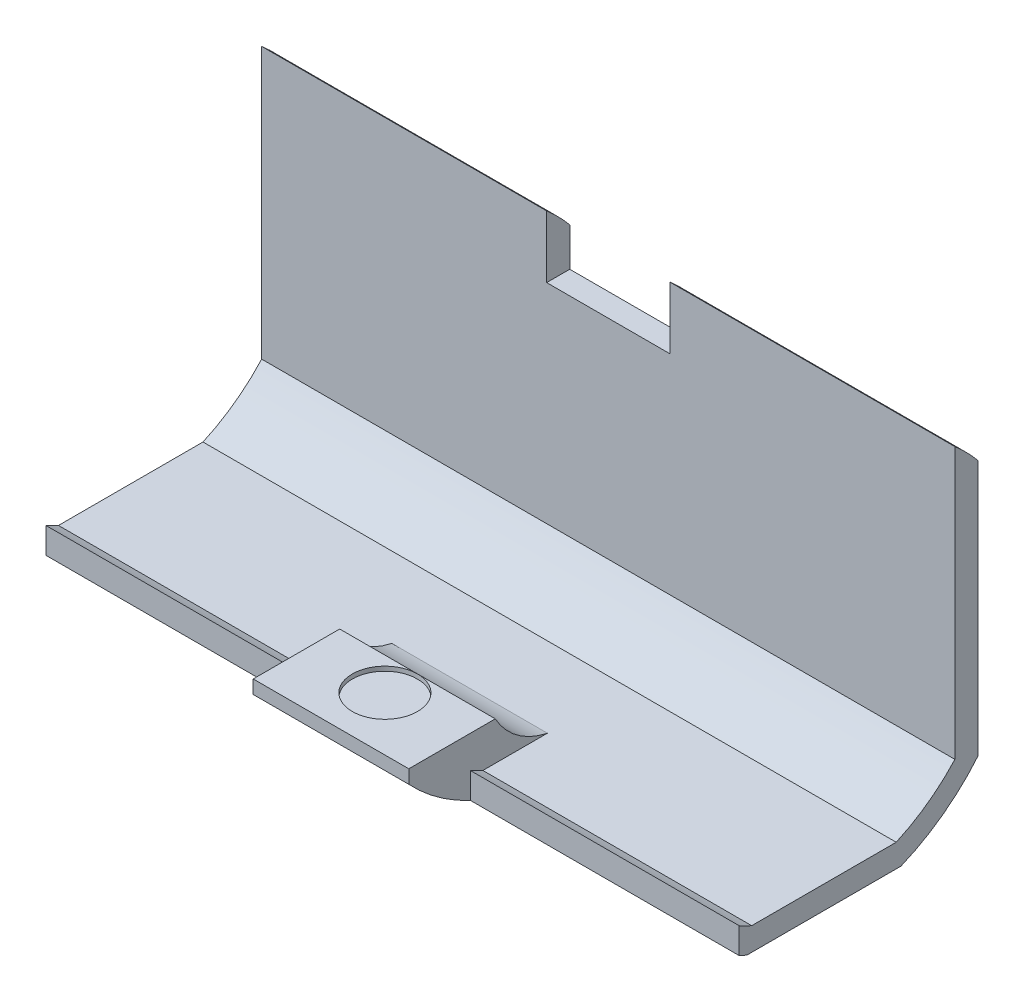
SolidWorks part; units mm, degrees
ref_plane "Plano frontal" through (0, 0, 0) normal (0, 0, 1) x (1, 0, 0)
ref_plane "Plano superior" through (0, 0, 0) normal (0, 1, 0) x (1, 0, 0)
ref_plane "Plano direito" through (0, 0, 0) normal (1, 0, 0) x (0, 0, -1)
sketch "Esboço2" plane through (0, 0, 0) normal (0, 0, 1) x (1, 0, 0)
  line L0 (0, 47.2571) -> (8.5, 47.2571)
  line L1 (0, 47.2571) -> (-8.5, 47.2571)
  line L2 (0, 23.9177) -> (8.5, 23.9177)
  line L3 (0, 23.9177) -> (-8.5, 23.9177)
  line L4 (0, 8.4) -> (0, 75) construction
  line L5 (0, 56.3545) -> (-16, 56.3545) construction
  line L6 (0, 56.3545) -> (16, 56.3545) construction
  line L7 (8.5, 47.2571) -> (8.5, 23.9177)
  line L8 (-8.5, 47.2571) -> (-8.5, 23.9177)
  line L20 (19.3117, 92) -> (-19.3117, 92)
  line L21 (-19.3117, 92) -> (-36.5, 70)
  line L22 (-36.5, 70) -> (-36.5, 0)
  line L23 (-36.5, 0) -> (-22.5, 0)
  line L24 (-22.5, 0) -> (-22.5, 8.4)
  line L25 (-22.5, 8.4) -> (22.5, 8.4)
  line L26 (22.5, 8.4) -> (22.5, 0)
  line L27 (22.5, 0) -> (36.5, 0)
  line L28 (36.5, 0) -> (36.5, 70)
  line L29 (36.5, 70) -> (19.3117, 92)
  circle A8 centre (29.2, 62) radius 2
  circle A9 centre (29.2, 49) radius 2
  circle A10 centre (29.2, 36) radius 2
  circle A11 centre (29.2, 23) radius 2
  circle A12 centre (-29.2, 23) radius 2
  circle A13 centre (0, 75) radius 2
  circle A14 centre (-7, 83.3) radius 2
  circle A15 centre (7, 83.3) radius 2
  circle A16 centre (-29.2, 36) radius 2
  circle A17 centre (-29.2, 49) radius 2
  circle A18 centre (-29.2, 62) radius 2
  circle A20 centre (-29.2, 10) radius 2
  circle A21 centre (29.2, 10) radius 2
  circle A26 centre (-16, 56.3545) radius 2.0867
  circle A27 centre (16, 56.3545) radius 2.0867
  point P31 (0, 23.9177)
  point P33 (0, 47.2571)
sketch "Model" plane through (0, 0, 0) normal (0, 0, 1) x (1, 0, 0)
  line L0 (-13.5, 51.7) -> (0, 51.7) construction
  line L1 (-22.5, 41.7) -> (0, 41.7) construction
  line L2 (0, 50.7729) -> (-23, 50.7729) construction
  line L3 (-22.5, 61.7) -> (-22.5, 41.7) construction
  line L4 (-22.5, 61.7) -> (0, 61.7) construction
  line L5 (-22.5, 61.7) -> (-21, 61.7) construction
  line L6 (-21, 61.7) -> (-21, 43.2) construction
  line L7 (0, 61.7) -> (0, 41.7) construction
  line L8 (0, 61.7) -> (0, 59.2) construction
  line L9 (0, 44.2) -> (0, 59.2)
  line L10 (-23, 63.7) -> (-23, 39.7)
  line L11 (-5.2, 59.2) -> (-0.8, 59.2) construction
  line L12 (-23, 63.7) -> (-5.55, 63.7)
  line L13 (0, 41.7) -> (0, 42.7) construction
  line L14 (-5.55, 63.7) -> (-5.55, 59.2)
  line L15 (0, 42.7) -> (-3.75, 42.7) construction
  line L16 (-3, 57) -> (-3, 61.4) construction
  line L17 (0, 59.2) -> (-5.55, 59.2)
  line L18 (-3, 61.4) -> (0, 61.4) construction
  line L19 (-3, 57) -> (0, 57) construction
  line L20 (-3.75, 41.7) -> (-3.75, 43.7) construction
  line L21 (0, 51.7) -> (-23, 51.7) construction
  line L22 (-3.75, 43.7) -> (0, 43.7) construction
  line L23 (-23, 39.7) -> (-5.55, 39.7)
  line L24 (-3.75, 41.7) -> (-3.75, 34.7) construction
  line L25 (-3.75, 34.7) -> (0, 34.7) construction
  line L26 (-5.55, 39.7) -> (-5.55, 44.2)
  line L27 (0, 44.2) -> (-5.55, 44.2)
  line L34 (-9.5, 39.7) -> (-17.5, 39.7) construction
  line L35 (-17.5, 39.7) -> (-25.5, 47.7) construction
  line L36 (-25.5, 47.7) -> (-25.5, 55.7) construction
  line L37 (-25.5, 55.7) -> (-17.5, 63.7) construction
  line L38 (-17.5, 63.7) -> (-9.5, 63.7) construction
  line L39 (-9.5, 63.7) -> (-5.55, 59.2) construction
  line L40 (-3, 46.75) -> (0, 46.75) construction
  line L41 (-3, 56.65) -> (0, 56.65) construction
  line L42 (-5.55, 44.2) -> (-5.55, 41.2) construction
  line L44 (-2.5, 36.75) -> (-5.55, 41.2) construction
  line L45 (-2.5, 36.75) -> (-2.5, 31.7) construction
  line L48 (-9.5, 31.7) -> (-9.5, 39.7) construction
  line L50 (-2.5, 31.7) -> (-2.5, 29.7) construction
  line L51 (-2.5, 29.7) -> (-9.5, 29.7) construction
  line L52 (-9.5, 29.7) -> (-9.5, 31.7) construction
  line L56 (-36.5, 50.7729) -> (-23.5, 50.7729) construction
  line L57 (-36.5, 70) -> (-36.5, 0) construction
  line L58 (0, 8.4) -> (0, 75) construction
  circle A0 centre (-13.5, 51.7) radius 8.35
  circle A2 centre (-21, 43.2) radius 1 construction
  circle A4 centre (-3, 59.2) radius 2.2 construction
  circle A7 centre (-13.5, 51.7) radius 8 construction
  arc A10 (-5.55, 59.2) -> (-3, 56.65) centre (-3, 59.2) ccw construction
  arc A11 (-3, 46.75) -> (-5.55, 44.2) centre (-3, 44.2) ccw construction
extrude "Ressalto-extrusão2" add sketch "Model" along normal blind 4
sketch "Esboço5" plane through (0, 0, 0) normal (0, 0, -1) x (-1, 0, 0)
  line L1 (23, 63.7) -> (25, 63.7)
  line L2 (23, 63.7) -> (23, 39.7)
  line L3 (23, 39.7) -> (25, 39.7)
  line L4 (25, 63.7) -> (25, 39.7)
extrude "Ressalto-extrusão3" add sketch "Esboço5" against normal blind 20
sketch "Esboço6" plane through (-25, 0, 0) normal (-1, 0, 0) x (0, 0, 1)
  line L0 (0, 51.7) -> (20, 51.7) construction
  line L1 (0, 39.7) -> (0, 63.7) construction
  line L2 (20, 39.7) -> (20, 63.7) construction
  line L3 (20, 51.7) -> (10, 63.7) construction
  line L4 (20, 63.7) -> (0, 63.7) construction
  line L5 (10, 63.7) -> (10, 39.7) construction
  line L6 (20, 39.7) -> (0, 39.7) construction
  circle A0 centre (10, 51.7) radius 13
extrude "Corte-extrusão1" cut sketch "Esboço6" against normal through all flip side to cut
sketch "Esboço8" plane through (-25, 0, 0) normal (-1, 0, 0) x (0, 0, 1)
  line L0 (10, 63.7) -> (10, 39.7) construction
  line L1 (15, 63.7) -> (5, 63.7) construction
  line L2 (15, 39.7) -> (5, 39.7) construction
  line L3 (10, 39.7) -> (0, 51.7) construction
  line L4 (0, 43.3934) -> (0, 60.0066) construction
  line L5 (0, 51.7) -> (20, 51.7) construction
  line L6 (20, 43.3934) -> (20, 60.0066) construction
  line L7 (10, 51.7) -> (7.885, 51.7) construction
  line L8 (10, 51.7) -> (8.5045, 53.1955) construction
  line L9 (10, 51.7) -> (10, 53.815) construction
  line L10 (10, 51.7) -> (11.4955, 53.1955) construction
  line L11 (10, 51.7) -> (12.115, 51.7) construction
  line L12 (10, 51.7) -> (11.4955, 50.2045) construction
  line L13 (10, 51.7) -> (10, 49.585) construction
  line L14 (10, 51.7) -> (8.5045, 50.2045) construction
  line L15 (7.885, 51.7) -> (10, 49.585)
  line L16 (10, 49.585) -> (12.115, 51.7)
  line L17 (12.115, 51.7) -> (10, 53.815)
  line L18 (10, 53.815) -> (7.885, 51.7)
  circle A0 centre (10, 51.7) radius 2.115 construction
  point P24 (10, 51.7)
  dimension "D1" = 8
extrude "Corte-extrusão2" cut sketch "Esboço8" against normal through all
mirror "Espelhar1" about plane through (0, 44.2, 4) normal (-1, 0, 0) of bodies 105
sketch "Esboço9" plane through (0, 0, 4) normal (0, 0, 1) x (1, 0, 0)
  line L0 (0, 59.2) -> (4, 59.2)
  line L1 (5.55, 59.2) -> (-5.55, 59.2) construction
  line L2 (4, 59.2) -> (4, 44.2)
  line L3 (-5.55, 44.2) -> (5.55, 44.2) construction
  line L4 (4, 44.2) -> (-4, 44.2)
  line L5 (-4, 44.2) -> (-4, 59.2)
  line L6 (-4, 59.2) -> (0, 59.2)
extrude "Ressalto-extrusão4" add sketch "Esboço9" along normal blind 4
sketch "Esboço10" plane through (0, 59.2, 0) normal (0, 1, 0) x (1, 0, 0)
  line L0 (0, 0) -> (0, -8) construction
  line L1 (4, -8) -> (-4, -8) construction
  line L2 (0, -4) -> (2.115, -4) construction
  line L3 (0, -4) -> (1.4955, -5.4955) construction
  line L4 (0, -4) -> (0, -6.115) construction
  line L5 (0, -4) -> (-1.4955, -5.4955) construction
  line L6 (0, -4) -> (-2.115, -4) construction
  line L7 (0, -4) -> (-1.4955, -2.5045) construction
  line L8 (0, -4) -> (0, -1.885) construction
  line L9 (0, -4) -> (1.4955, -2.5045) construction
  line L10 (0, -1.885) -> (-2.115, -4)
  line L11 (-2.115, -4) -> (0, -6.115)
  line L12 (0, -6.115) -> (2.115, -4)
  line L13 (2.115, -4) -> (0, -1.885)
  point P17 (0, -4)
  dimension "D1" = 8
extrude "Corte-extrusão3" cut sketch "Esboço10" against normal through all
sketch "Esboço13" plane through (23, 0, 0) normal (-1, 0, 0) x (0, 0, 1)
  line L0 (18.5, 43.954) -> (18.5, 59.446)
  line L1 (14.6904, 62.2) -> (5.3096, 62.2)
  line L2 (18.5, 43.954) -> (18.5, 41.8638)
  line L3 (4.5, 63.4792) -> (4.5, 61.7995)
  line L4 (15, 63.7) -> (5, 63.7)
  line L5 (4, 63.2326) -> (4, 40.1674)
  line L6 (5, 39.7) -> (15, 39.7)
  line L7 (20, 43.3934) -> (20, 60.0066)
  line L8 (15, 63.7) -> (5, 63.7)
  line L11 (20, 43.3934) -> (20, 60.0066)
  arc A0 (15, 39.7) -> (20, 43.3934) centre (10, 51.7) ccw construction
  arc A1 (18.5, 59.446) -> (14.6904, 62.2) centre (10, 51.7) ccw
  arc A2 (5.3096, 62.2) -> (4.5, 61.7995) centre (10, 51.7) ccw
  arc A3 (5.3096, 62.2) -> (4.6923, 61.9019) centre (10, 51.7) ccw construction
  arc A4 (5, 63.7) -> (4, 63.2326) centre (10, 51.7) ccw
  arc A5 (4, 40.1674) -> (5, 39.7) centre (10, 51.7) ccw
  arc A6 (15, 39.7) -> (20, 43.3934) centre (10, 51.7) ccw
  arc A7 (20, 60.0066) -> (15, 63.7) centre (10, 51.7) ccw
  arc A8 (5, 63.7) -> (4.5, 63.4792) centre (10, 51.7) ccw
  arc A9 (5, 63.7) -> (4, 63.2326) centre (10, 51.7) ccw construction
  arc A10 (18.5, 41.8638) -> (20, 43.3934) centre (10, 51.7) ccw
  arc A11 (20, 60.0066) -> (15, 63.7) centre (10, 51.7) ccw
  arc A12 (14.4231, 41.0846) -> (18.5, 43.954) centre (10, 51.7) ccw construction
  dimension "D1" = 0
  dimension "D2" = 1.5
extrude "Ressalto-extrusão5" add sketch "Esboço13" along normal blind 45 from offset 0.5
sketch "Esboço14" plane through (0, 59.2, 0) normal (0, 1, 0) x (1, 0, 0)
  line L0 (5.05, -4) -> (5.05, -8)
  line L1 (0, -6.115) -> (2.115, -4) construction
  line L2 (1.0575, -5.0575) -> (-1.1584, -2.8416) construction
  line L3 (-1.1584, -2.8416) -> (1.0575, -2.9425) construction
  line L4 (2.115, -4) -> (0, -1.885) construction
  line L5 (1.0575, -2.9425) -> (-1.0575, -5.0575) construction
  line L6 (-2.115, -4) -> (0, -6.115) construction
  line L7 (5.05, -8) -> (4, -8) construction
  line L8 (5.55, 0) -> (-5.55, 0)
  line L9 (-5.55, 0) -> (-5.55, -4)
  line L10 (-5.55, -4) -> (-4, -4)
  line L11 (-4, -4) -> (-4, -8)
  line L12 (-4, -8) -> (4, -8)
  line L13 (4, -8) -> (4, -4)
  line L14 (4, -4) -> (5.55, -4)
  line L15 (5.55, -4) -> (5.55, 0)
  line L16 (-5.05, -4) -> (-5.05, -8)
  line L17 (-5.05, -8) -> (-4, -8) construction
  line L18 (-5.05, -8) -> (-5.05, -9.5)
  line L19 (-5.05, -9.5) -> (5.05, -9.5)
  line L20 (-4, -8) -> (4, -8) construction
  line L21 (5.05, -9.5) -> (5.05, -8)
  line L24 (5.05, -4) -> (5.05, -0.5)
  line L26 (5.05, -0.5) -> (-5.05, -0.5)
  line L27 (-5.05, -0.5) -> (-5.05, -4)
  circle A0 centre (0, -4) radius 2.115
  dimension "D1" = 0
extrude "Ressalto-extrusão6" add sketch "Esboço14" along normal up to vertex (4.2792 mm away) from offset 0.5 up to point (-22.5, 63.4792, 4.5)
sketch "Esboço15" plane through (5.05, 0, 0) normal (1, 0, 0) x (0, 0, -1)
  line L0 (-5.5617, 63.9189) -> (-4.5, 63.9189)
  line L1 (-4.5, 63.9189) -> (-4.5, 64.9791)
  line L2 (-4.5, 64.9791) -> (0, 64.9791)
  line L3 (0, 64.9791) -> (0, 60.0066)
  arc A0 (0, 60.0066) -> (-4, 63.2326) centre (-10, 51.7) ccw construction
  arc A1 (0, 60.0066) -> (-5.5617, 63.9189) centre (-10, 51.7) ccw
extrude "Corte-extrusão4" cut sketch "Esboço15" against normal up to surface (10.1 mm away) up to face at (-5.05, 61.7951, 4.9008)
sketch "Esboço17" plane through (0, 63.7, 0) normal (0, 1, 0) x (1, 0, 0)
  circle A0 centre (0, -4) radius 3.5
sketch "Esboço18" plane through (0, 0, 20) normal (0, 0, 1) x (1, 0, 0)
  line L0 (-4, 45.8934) -> (0, 45.8934)
  line L2 (0, 45.8934) -> (4, 45.8934)
  line L3 (4, 45.8934) -> (4, 37.8132)
  line L4 (4, 37.8132) -> (-4, 37.8132)
  line L5 (-4, 37.8132) -> (-4, 45.8934)
extrude "Corte-extrusão7" cut sketch "Esboço18" against normal blind 10
extrude "Corte-extrusão8" cut sketch "Esboço17" against normal blind 2
sketch "Esboço21" plane through (5.05, 0, 0) normal (1, 0, 0) x (0, 0, -1)
  line L0 (-9.5, 59.7) -> (8, 59.7) construction
  line L1 (-9.5, 59.7) -> (-0.5, 59.7) construction
  line L2 (-6.115, 59.7) -> (-1.885, 59.7) construction
  line L3 (-6.115, 59.7) -> (-1.885, 59.7) construction
  line L4 (-6.115, 59.7) -> (-9.5, 59.7)
  line L5 (-9.5, 59.7) -> (-9.5, 62.2)
  arc A0 (-9.5, 62.2) -> (-6.115, 59.7) centre (-10.5021, 57.3015) cw
extrude "Corte-extrusão11" cut sketch "Esboço21" against normal up to surface (10.1 mm away) up to face at (-5.05, 61.4075, 4.8809)
move or copy body "Corpo-Mover/Copiar1" bodies to move or copy 108 copy no translate (0, 0, -38.6991)
sketch "Esboço19" plane through (0, 63.7, 0) normal (0, 1, 0) x (1, 0, 0)
  line L1 (-34.2602, 14.0031) -> (32.7464, 14.0031)
  line L2 (-34.2602, 14.0031) -> (-34.2602, 42.2081)
  line L3 (-34.2602, 42.2081) -> (32.7464, 42.2081)
  line L4 (32.7464, 14.0031) -> (32.7464, 42.2081)
extrude "Corte-extrusão9" cut sketch "Esboço19" against normal through all
move or copy body "Corpo-Mover/Copiar2" bodies to move or copy 124 copy no rotation origin (0, 0, 0) rotation axis (1, 0, 0) rotation angle 180
sketch "Esboço25" plane through (0, 0, -0.5) normal (0, 0, 1) x (1, 0, 0)
  line L0 (2.115, -59.7) -> (-2.115, -59.7) construction
  line L2 (0, -59.7) -> (0, -60.5741) construction
  line L3 (-5.05, -60.5741) -> (5.05, -60.5741) construction
  line L4 (2.115, -59.9871) -> (2.115, -60.1371)
  line L5 (2.115, -60.1371) -> (2.115, -60.2871)
  line L6 (2.115, -60.2871) -> (-2.115, -60.2871)
  line L7 (-2.115, -60.2871) -> (-2.115, -59.9871)
  line L8 (-2.115, -59.9871) -> (2.115, -59.9871)
extrude "suporte2" add sketch "Esboço25" against normal blind 5.6
